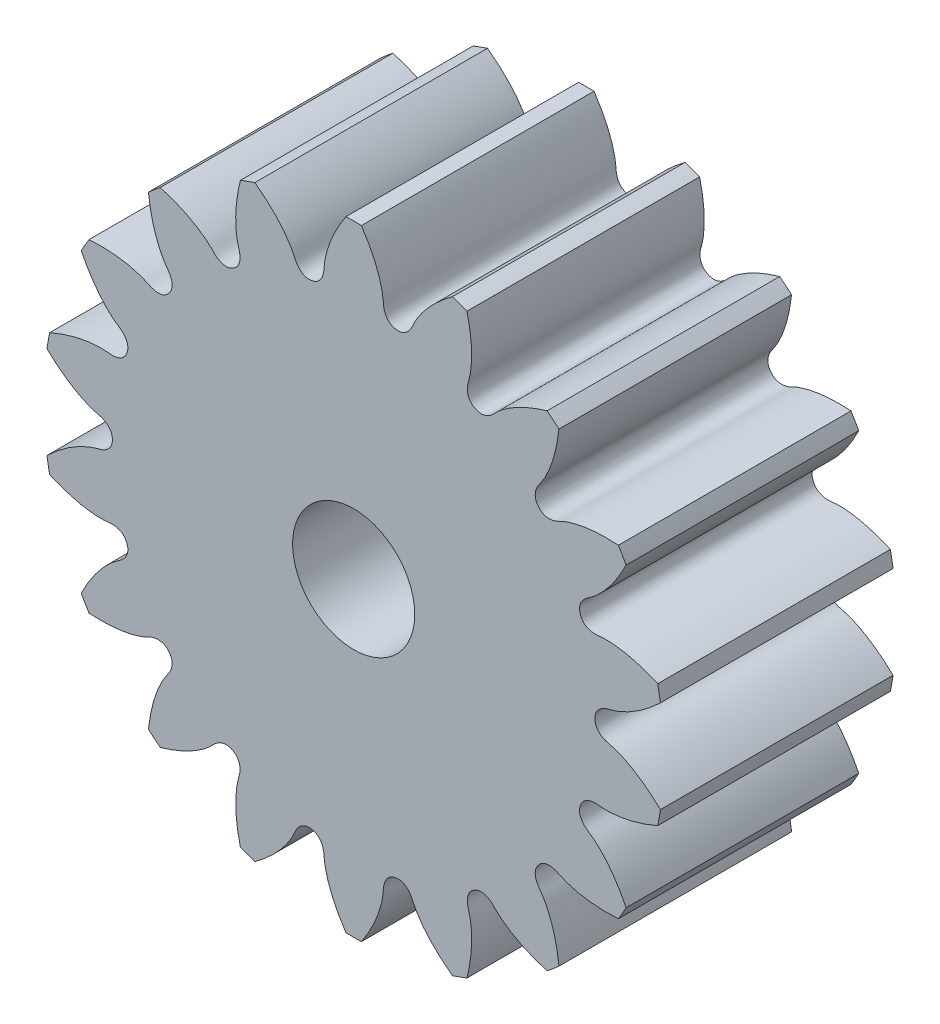
SolidWorks part; units mm, degrees
ref_plane "Front Plane" through (0, 0, 0) normal (0, 0, 1) x (1, 0, 0)
ref_plane "Top Plane" through (0, 0, 0) normal (0, 1, 0) x (1, 0, 0)
ref_plane "Right Plane" through (0, 0, 0) normal (1, 0, 0) x (0, 0, -1)
ref_axis "Axis1" through (0, 0, 10.4775) along (0, 0, -1)
sketch "SketchRevolveSpurPinion" plane through (0, 0, 0) normal (1, 0, 0) x (0, 0, -1)
  line L0 (0, 0) -> (1, 0) construction
  line L1 (-9.525, 0) -> (-9.525, 25.4)
  line L2 (-9.525, 25.4) -> (9.525, 25.4)
  line L3 (9.525, 25.4) -> (9.525, 0)
  line L4 (9.525, 0) -> (-9.525, 0)
  dimension "Side1" = 9.525
  dimension "OutsideRadius" = 25.4
  dimension "Side2" = 9.525
revolve "SpurPinion" add sketch "SketchRevolveSpurPinion" angle 360 about L0
sketch "SketchToothSpurPinion" plane through (0, 0, 0) normal (0, 0, 1) x (1, 0, 0)
  arc A0 (25.228, 3.8953) -> (25.228, -3.8953) centre (0, 0) cw
  spline S0 degree 3 poles (25.228, -3.8953) (24.9857, -3.657) (24.6199, -3.3209) (24.1221, -2.9121) (23.77, -2.6435) (23.4304, -2.4032) (23.1048, -2.19) (22.7948, -2.0026) (22.5016, -1.8394) (22.2267, -1.6991) (21.9713, -1.5801) (21.7365, -1.4808) (21.5233, -1.3994) (21.3327, -1.3348) (21.0878, -1.2597) (20.8813, -1.2184) (20.7165, -1.1664) (20.6573, -1.1459) (20.599, -1.1238) (20.5416, -1.1) (20.4852, -1.0744) (20.4295, -1.0468) (20.3747, -1.0171) (20.3207, -0.985) (20.2674, -0.9503) (20.2149, -0.9127) (20.1633, -0.872) (20.1127, -0.8276) (20.0632, -0.7793) (20.0153, -0.7267) (19.9692, -0.6693) (19.9255, -0.6069) (19.8851, -0.5391) (19.8486, -0.4659) (19.8172, -0.3874) (19.7918, -0.3042) (19.7733, -0.217) (19.7639, -0.1336) (19.7605, -0.061) (19.7615, 0) (19.7605, 0.061) (19.7639, 0.1336) (19.7733, 0.217) (19.7918, 0.3042) (19.8172, 0.3874) (19.8486, 0.4659) (19.8851, 0.5391) (19.9255, 0.6069) (19.9692, 0.6693) (20.0153, 0.7267) (20.0632, 0.7793) (20.1127, 0.8276) (20.1633, 0.872) (20.2149, 0.9127) (20.2674, 0.9503) (20.3207, 0.985) (20.3747, 1.0171) (20.4295, 1.0468) (20.4852, 1.0744) (20.5416, 1.1) (20.599, 1.1238) (20.6573, 1.1459) (20.7165, 1.1664) (20.8813, 1.2184) (21.0878, 1.2597) (21.3327, 1.3348) (21.5233, 1.3994) (21.7365, 1.4808) (21.9713, 1.5801) (22.2267, 1.6991) (22.5016, 1.8394) (22.7948, 2.0026) (23.1048, 2.19) (23.4304, 2.4032) (23.77, 2.6435) (24.1221, 2.9121) (24.6199, 3.3209) (24.9857, 3.657) (25.228, 3.8953) knots 0 0 0 0 0.0732 0.106911 0.138695 0.168553 0.196485 0.22249 0.246569 0.268721 0.288948 0.307248 0.323622 0.338069 0.35059 0.378768 0.383302 0.3878 0.39227 0.396724 0.40117 0.405622 0.410094 0.4146 0.419156 0.423782 0.428495 0.433317 0.438269 0.443372 0.448646 0.454107 0.459768 0.465633 0.471698 0.477947 0.484352 0.490873 0.495999 0.5 0.504001 0.509127 0.515648 0.522053 0.528302 0.534367 0.540232 0.545893 0.551354 0.556628 0.561731 0.566683 0.571505 0.576218 0.580844 0.5854 0.589906 0.594378 0.59883 0.603276 0.60773 0.6122 0.616698 0.621232 0.64941 0.661931 0.676378 0.692752 0.711052 0.731279 0.753431 0.77751 0.803515 0.831447 0.861305 0.893089 0.9268 1 1 1 1
extrude "ToothExtrudeCutSpurPinion" cut sketch "SketchToothSpurPinion" against normal blind 9.525 and the other way blind 9.525
pattern_circular "PatternSpurPinion" count 18 every 20 about axis through (0, 0, 10.4775) along (0, 0, -1) of "ToothExtrudeCutSpurPinion"
sketch "AuxiliarySketchSpurPinion" plane through (0, 0, 0) normal (0, 0, 1) x (1, 0, 0)
  circle A0 centre (0, 0) radius 22.86 construction
  circle A1 centre (0, 0) radius 20.7182 construction
  circle A2 centre (0, 0) radius 20.9904 construction
  circle A3 centre (0, 0) radius 25.4 construction
  circle A4 centre (0, 0) radius 19.7612 construction
  dimension "PitchDiameter" = 45.72
  dimension "BaseDiameter" = 41.4364
  dimension "FormDiameter" = 41.9809
  dimension "MajorDiameter" = 50.8
  dimension "MinorDiameter" = 39.5224
scale "Scale1" bodies to scale 103 scale about centroid uniform scaling yes scale factor 0.5
sketch "Sketch1" plane through (0, 0, 4.7625) normal (0, 0, 1) x (1, 0, 0)
  circle A0 centre (0, 0) radius 2.5
  dimension "D1" = 5
extrude "Cut-Extrude1" cut sketch "Sketch1" against normal blind 7
sketch "Sketch2" plane through (0, 0, -4.7625) normal (0, 0, -1) x (-1, 0, 0)
  circle A0 centre (0, 0) radius 4.4579
extrude "Cut-Extrude2" cut sketch "Sketch2" against normal blind 2
